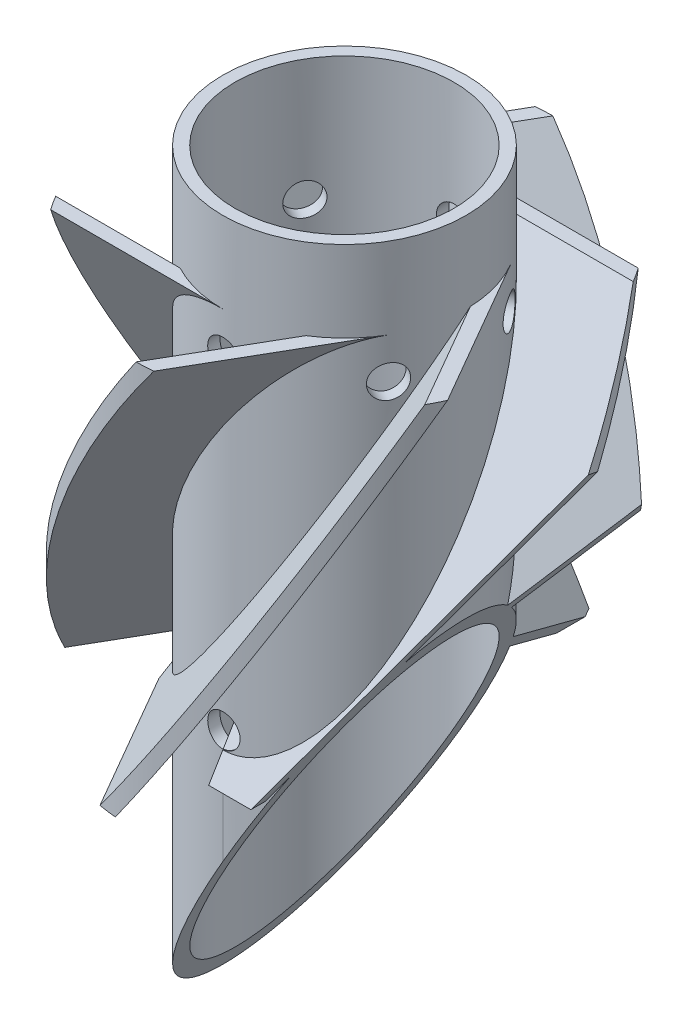
SolidWorks part; units mm, degrees
ref_plane "前视基准面" through (0, 0, 0) normal (0, 0, 1) x (1, 0, 0)
ref_plane "上视基准面" through (0, 0, 0) normal (0, 1, 0) x (1, 0, 0)
ref_plane "右视基准面" through (0, 0, 0) normal (1, 0, 0) x (0, 0, -1)
sketch "草图1" plane through (0, 0, 0) normal (0, 1, 0) x (1, 0, 0)
  circle A0 centre (0, 0) radius 27
  circle A1 centre (0, 0) radius 30
  dimension "D1" = 60
  dimension "D2" = 54
extrude "凸台-拉伸1" add sketch "草图1" along normal blind 190
ref_axis "基准轴1" through (0, 190, 0) along (0, -1, 0)
ref_plane "基准面2" through (0, 170, 0) normal (0, 1, 0) x (1, 0, 0)
ref_plane "基准面3" through (0, 70, 0) normal (0, 1, 0) x (1, 0, 0)
sketch "草图2" plane through (0, 70, 0) normal (0, 1, 0) x (1, 0, 0)
  line L0 (0, 30) -> (0, -30) construction
  line L1 (-25.9808, 15) -> (25.9808, -15) construction
  line L2 (-26.0281, -14.9177) -> (25.9332, 15.0821) construction
  circle A0 centre (0, 0) radius 30 construction
  dimension "D2" = 60
  dimension "D3" = 60
sketch "草图4" plane through (0, 170, 0) normal (0, 1, 0) x (1, 0, 0)
  line L0 (-25.9808, 15) -> (25.9808, -15) construction
  line L7 (0, 30) -> (0, -30) construction
  line L8 (-26.0281, -14.9177) -> (25.9332, 15.0821) construction
ref_axis "基准轴2" through (-26.0281, 170, 14.9177) along (0.4456, -0.8575, -0.2572)
ref_axis "基准轴3" through (0, 170, 30) along (0, -0.8575, -0.5145)
ref_axis "基准轴4" through (25.9332, 170, -15.0821) along (-0.4456, -0.8575, 0.2572)
ref_axis "基准轴5" through (-25.9808, 170, -15) along (0.4456, -0.8575, 0.2572)
ref_axis "基准轴6" through (0, 170, -30) along (0, -0.8575, 0.5145)
ref_axis "基准轴7" through (-25.9808, 70, -15) along (0.4456, 0.8575, 0.2572)
sketch "草图5" plane through (0, 0, 0) normal (1, 0, 0) x (0, 0, -1)
  line L0 (-30, 190) -> (-30, 160) construction
  line L1 (-30, 190) -> (-30, 0) construction
  line L2 (-30, 160) -> (30, 160) construction
  line L3 (30, 0) -> (30, 190) construction
  line L4 (-30, 160) -> (-30, 80) construction
  line L5 (-30, 80) -> (30, 80) construction
  circle A0 centre (0, 160) radius 4
  circle A1 centre (0, 80) radius 4
  dimension "D3" = 8
  dimension "D4" = 8
  dimension "D1" = 30
  dimension "D2" = 80
ref_plane "基准面4" through (0, 31.7647, 52.9412) normal (0, 0.5145, 0.8575) x (0, -0.8575, 0.5145)
sketch "草图7" plane through (0, 0, 0) normal (0, 0, 1) x (1, 0, 0)
  line L0 (-29.9835, 190) -> (-29.9835, 160) construction
  line L1 (30, 190) -> (-30, 190) construction
  line L2 (-29.9835, 160) -> (-30, 80) construction
  line L3 (-30, 190) -> (-30, 0) construction
  line L4 (-29.9835, 160) -> (30, 160) construction
  line L5 (30, 0) -> (30, 190) construction
  line L6 (-30, 80) -> (30, 80) construction
  circle A0 centre (0, 80) radius 4
  circle A1 centre (0.0083, 160) radius 4
  dimension "D3" = 8
  dimension "D4" = 8
  dimension "D1" = 30
  dimension "D2" = 80
extrude "切除-拉伸2" cut sketch "草图7" against normal through all
pattern_circular "阵列(圆周)2" count 6 over 360 about axis through (0, 190, 0) along (0, -1, 0) of "切除-拉伸2" reverse direction yes
sketch "草图6" plane through (0, 31.7647, 52.9412) normal (0, 0.5145, 0.8575) x (0, -0.8575, 0.5145)
  line L2 (-161.2087, 60) -> (-38.7755, 60)
  line L3 (-38.7755, 60) -> (-38.7755, 0)
  line L4 (-162.9237, 0) -> (0, 0) construction
  line L5 (-38.7755, 0) -> (-161.2087, 0)
  line L6 (-161.2087, 0) -> (-161.2087, 60)
  dimension "D1" = 60
extrude "凸台-拉伸2" add sketch "草图6" along normal blind 3
pattern_circular "阵列(圆周)3" count 6 over 360 about axis through (0, 190, 0) along (0, -1, 0) of "凸台-拉伸2" reverse direction yes
ref_plane "基准面5" through (0, 190, 0) normal (0, 1, 0) x (1, 0, 0)
sketch "草图9" plane through (0, 190, 0) normal (0, 1, 0) x (1, 0, 0)
  circle A0 centre (0, 0) radius 30
  circle A1 centre (0, 0) radius 77.3626
  dimension "D1" = 60
extrude "切除-拉伸3" cut sketch "草图9" against normal blind 20
sketch "草图10" plane through (0, 190, 0) normal (0, 1, 0) x (1, 0, 0)
  circle A0 centre (0, 0) radius 90.8687
  circle A1 centre (0, 0) radius 52
  dimension "D1" = 104
extrude "切除-拉伸4" cut sketch "草图10" against normal blind 190
sketch "草图11" plane through (0, 0, 0) normal (0, 1, 0) x (1, 0, 0)
  circle A0 centre (0, 0) radius 30
  circle A1 centre (0, 0) radius 68.5027
  dimension "D1" = 60
extrude "切除-拉伸5" cut sketch "草图11" along normal blind 70
sketch "草图12" plane through (0, 0, 0) normal (0, 0, 1) x (1, 0, 0)
  line L0 (-30, 0) -> (75.0898, 182.0209)
  line L1 (75.0898, 182.0209) -> (75.0898, 0)
  line L2 (75.0898, 0) -> (-30, 0)
  dimension "D1" = 60
extrude "切除-拉伸6" cut sketch "草图12" against normal through all both and the other way through all
sketch "草图13" plane through (0, 0, 0) normal (0, 1, 0) x (1, 0, 0)
  circle A0 centre (0, 0) radius 27
extrude "切除-拉伸7" cut sketch "草图13" along normal through all
